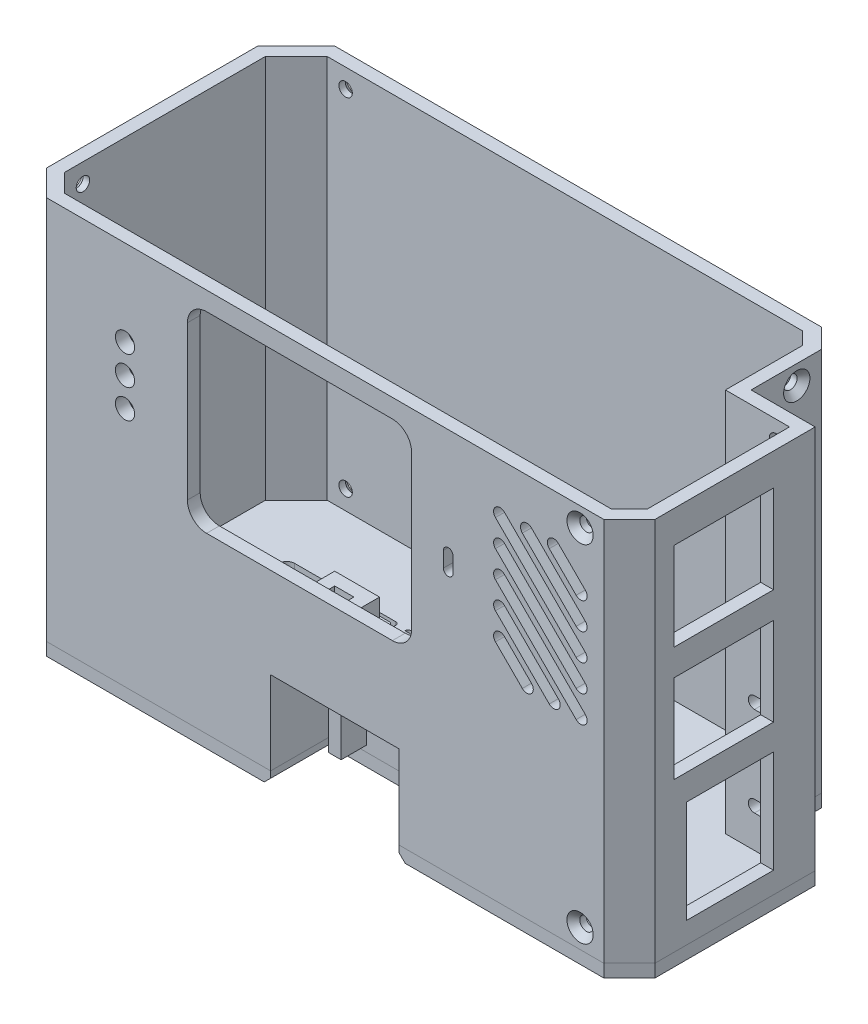
SolidWorks part; units mm, degrees
ref_plane "前视基准面" through (0, 0, 0) normal (0, 0, 1) x (1, 0, 0)
ref_plane "上视基准面" through (0, 0, 0) normal (0, 1, 0) x (1, 0, 0)
ref_plane "右视基准面" through (0, 0, 0) normal (1, 0, 0) x (0, 0, -1)
other "Configuration Table"
sketch "草图1" plane through (0, 0, 0) normal (0, 0, 1) x (1, 0, 0)
  line L1 (-105.5174, 35.9027) -> (-10.5174, 35.9027)
  line L2 (-105.5174, 35.9027) -> (-105.5174, -26.0973)
  line L3 (-105.5174, -26.0973) -> (-10.5174, -26.0973)
  line L4 (-10.5174, 35.9027) -> (-10.5174, -26.0973)
  dimension "D1" = 62
  dimension "D2" = 95
extrude "凸台-拉伸1" add sketch "草图1" along normal blind 43
sketch "草图4" plane through (0, -26.0973, 0) normal (0, -1, 0) x (1, 0, 0)
  line L0 (-10.5174, 43) -> (-10.5174, 0) construction
  line L1 (-10.5174, 14) -> (-20.5174, 14)
  line L2 (-10.5174, 14) -> (-10.5174, 0)
  line L3 (-10.5174, 0) -> (-20.5174, 0)
  line L4 (-20.5174, 14) -> (-20.5174, 0)
  line L5 (-105.5174, 0) -> (-10.5174, 0) construction
  dimension "D1" = 14
  dimension "D2" = 10
extrude "切除-拉伸3" cut sketch "草图4" against normal up to next
chamfer "倒角2" distance 6 angle 45 1 edges at (-105.5174, 4.9027, 0)
chamfer "倒角3" distance 4 angle 45 2 edges at (-105.5174, 4.9027, 43) (-10.5174, 4.9027, 43)
sketch "草图7" plane through (0, 0, 43) normal (0, 0, 1) x (1, 0, 0)
  line L0 (-101.5174, -26.0973) -> (-14.5174, -26.0973) construction
  line L1 (-46.5174, -26.0973) -> (-66.5174, -26.0973)
  line L2 (-46.5174, -26.0973) -> (-46.5174, -6.0973)
  line L3 (-46.5174, -6.0973) -> (-66.5174, -6.0973)
  line L4 (-66.5174, -26.0973) -> (-66.5174, -6.0973)
  line L6 (-10.5174, -26.0973) -> (-10.5174, 35.9027) construction
  dimension "D1" = 36
  dimension "D2" = 20
  dimension "D3" = 20
extrude "切除-拉伸5" cut sketch "草图7" against normal blind 10
shell "抽壳3" thickness 2 removed face at (-54.2952, 35.9027, 22)
sketch "草图9" plane through (0, -6.0973, 0) normal (0, -1, 0) x (1, 0, 0)
  line L0 (-44.5174, 41) -> (-68.5174, 41) construction
  line L1 (-46.5174, 41) -> (-66.5174, 41)
  line L2 (-46.5174, 41) -> (-46.5174, 33)
  line L3 (-46.5174, 33) -> (-66.5174, 33)
  line L4 (-66.5174, 41) -> (-66.5174, 33)
  line L5 (-66.5174, 33) -> (-46.5174, 33) construction
  line L8 (-66.5174, 33) -> (-66.5174, 43) construction
  line L9 (-46.5174, 33) -> (-46.5174, 43) construction
extrude "切除-拉伸6" cut sketch "草图9" against normal blind 10
sketch "草图10" plane through (0, -6.0973, 0) normal (0, -1, 0) x (1, 0, 0)
  line L4 (-66.5174, 43) -> (-66.5174, 41)
  line L5 (-66.5174, 41) -> (-46.5174, 41)
  line L6 (-46.5174, 41) -> (-46.5174, 43)
  line L7 (-46.5174, 43) -> (-66.5174, 43)
  line L8 (-66.5174, 43) -> (-66.5174, 41)
  line L9 (-66.5174, 41) -> (-46.5174, 41)
  line L10 (-46.5174, 41) -> (-46.5174, 43)
  line L11 (-46.5174, 43) -> (-66.5174, 43)
  dimension "D1" = 0
extrude "凸台-拉伸2" add sketch "草图10" along normal blind 5
sketch "草图11" plane through (0, 0, 43) normal (0, 0, 1) x (1, 0, 0)
  line L0 (-97.0174, 3.0227) -> (-76.0174, 3.0227) construction
  line L1 (-44.5121, 32.986) -> (-79.5174, 32.986)
  line L2 (-44.5121, 32.986) -> (-44.5121, 3.0227)
  line L3 (-44.5121, 3.0227) -> (-79.5174, 3.0227)
  line L4 (-79.5174, 32.986) -> (-79.5174, 3.0227)
  arc A0 (-44.0174, 32.8768) -> (-45.0174, 33.0227) centre (-45.0174, 29.5227) ccw construction
extrude "切除-拉伸7" cut sketch "草图11" against normal blind 2
fillet "圆角5" radius 3 4 edges at (-79.5174, 32.986, 42) (-79.5174, 3.0227, 42) (-44.5121, 32.986, 42) (-44.5121, 3.0227, 42)
sketch "草图12" plane through (0, 0, 33) normal (0, 0, 1) x (1, 0, 0)
  line L0 (-46.5174, -4.0973) -> (-66.5174, -4.0973) construction
  line L1 (-63.5174, -4.0973) -> (-49.5174, -4.0973)
  line L2 (-63.5174, -4.0973) -> (-63.5174, -23.0973)
  line L3 (-63.5174, -23.0973) -> (-49.5174, -23.0973)
  line L4 (-49.5174, -4.0973) -> (-49.5174, -23.0973)
  line L5 (-66.5174, -4.0973) -> (-66.5174, -11.0973) construction
  line L6 (-46.5174, -4.0973) -> (-46.5174, -11.0973) construction
  line L7 (-66.5174, -26.0973) -> (-46.5174, -26.0973) construction
  dimension "D1" = 3
  dimension "D2" = 3
  dimension "D3" = 3
extrude "凸台-拉伸3" add sketch "草图12" along normal blind 4
sketch "草图13" plane through (0, -4.0973, 0) normal (0, 1, 0) x (1, 0, 0)
  line L0 (-44.5174, -31) -> (-68.5174, -31) construction
  line L1 (-61.5174, -31) -> (-51.5174, -31)
  line L2 (-61.5174, -31) -> (-61.5174, -35.5752)
  line L3 (-61.5174, -35.5752) -> (-51.5174, -35.5752)
  line L4 (-51.5174, -31) -> (-51.5174, -35.5752)
  line L5 (-68.5174, -31) -> (-68.5174, -41) construction
  line L6 (-44.5174, -31) -> (-44.5174, -41) construction
  dimension "D1" = 7
  dimension "D2" = 7
extrude "切除-拉伸8" cut sketch "草图13" against normal blind 17
sketch "草图14" plane through (0, 0, 37) normal (0, 0, 1) x (1, 0, 0)
  line L0 (-63.5174, -23.0973) -> (-49.5174, -23.0973) construction
  line L1 (-61.5174, -4.0973) -> (-51.5174, -4.0973)
  line L2 (-61.5174, -4.0973) -> (-61.5174, -23.0973)
  line L3 (-61.5174, -23.0973) -> (-51.5174, -23.0973)
  line L4 (-51.5174, -4.0973) -> (-51.5174, -23.0973)
extrude "切除-拉伸9" cut sketch "草图14" against normal up to surface (4 mm away) up to face at (-56.5174, -14.3473, 33)
chamfer "倒角4" distance 1 angle 45 2 edges at (-66.5174, -26.0973, 38) (-46.5174, -26.0973, 38)
sketch "草图15" plane through (-10.5174, 0, 0) normal (1, 0, 0) x (0, 0, -1)
  line L1 (-34.05, -4.7773) -> (-20.5, -4.7773)
  line L2 (-34.05, -4.7773) -> (-34.05, -20.7773)
  line L3 (-34.05, -20.7773) -> (-20.5, -20.7773)
  line L4 (-20.5, -4.7773) -> (-20.5, -20.7773)
  line L5 (-36, 13.0027) -> (-20.5, 13.0027)
  line L6 (-36, 13.0027) -> (-36, -0.7573)
  line L7 (-36, -0.7573) -> (-20.5, -0.7573)
  line L8 (-20.5, 13.0027) -> (-20.5, -0.7573)
  line L9 (-36, 30.9027) -> (-20.5, 30.9027)
  line L10 (-36, 30.9027) -> (-36, 17.1427)
  line L11 (-36, 17.1427) -> (-20.5, 17.1427)
  line L12 (-20.5, 30.9027) -> (-20.5, 17.1427)
extrude "切除-拉伸10" cut sketch "草图15" against normal blind 2
sketch "草图16" plane through (0, 0, 43) normal (0, 0, 1) x (1, 0, 0)
  line L0 (-38.7974, 19.2043) -> (-38.7974, 16.8043) construction
  line L1 (-38.0444, 19.2043) -> (-38.0444, 16.8043)
  line L2 (-39.5504, 19.2043) -> (-39.5504, 16.8043)
  line L3 (-44.5121, 29.986) -> (-44.5121, 6.0227) construction
  line L5 (-44.5121, 18.0043) -> (-51.3378, 18.0043) construction
  line L6 (-10.5174, -26.0973) -> (-10.5174, 35.9027) construction
  arc A0 (-38.0444, 19.2043) -> (-39.5504, 19.2043) centre (-38.7974, 19.2043) ccw
  arc A1 (-39.5504, 16.8043) -> (-38.0444, 16.8043) centre (-38.7974, 16.8043) ccw
  point P2 (-38.7974, 18.0043)
  point P14 (-44.5121, 18.0043)
  dimension "D1" = 2.4
  dimension "D2" = 28.28
extrude "切除-拉伸11" cut sketch "草图16" against normal blind 2
sketch "草图17" plane through (0, -26.0973, 0) normal (0, -1, 0) x (1, 0, 0)
  line L0 (-105.5174, 39) -> (-105.5174, 6) construction
  line L1 (-93.9174, 13.067) -> (-84.4174, 13.067)
  line L2 (-93.9174, 13.067) -> (-93.9174, 16.567)
  line L3 (-93.9174, 16.567) -> (-84.4174, 16.567)
  line L4 (-84.4174, 13.067) -> (-84.4174, 16.567)
  line L6 (-93.9174, 20.3114) -> (-84.4174, 20.3114)
  line L7 (-93.9174, 20.3114) -> (-93.9174, 23.8114)
  line L8 (-93.9174, 23.8114) -> (-84.4174, 23.8114)
  line L9 (-84.4174, 20.3114) -> (-84.4174, 23.8114)
  line L10 (-78.1448, 23.5342) -> (-71.5448, 23.5342)
  line L11 (-78.1448, 23.5342) -> (-78.1448, 20.3114)
  line L12 (-78.1448, 20.3114) -> (-71.5448, 20.3114)
  line L13 (-71.5448, 23.5342) -> (-71.5448, 20.3114)
  line L14 (-64.6448, 23.6466) -> (-58.0448, 23.6466)
  line L15 (-64.6448, 23.6466) -> (-64.6448, 20.3114)
  line L16 (-64.6448, 20.3114) -> (-58.0448, 20.3114)
  line L17 (-58.0448, 23.6466) -> (-58.0448, 20.3114)
  line L19 (-83.4263, 17.1002) -> (-76.4263, 17.1002)
  line L20 (-83.4263, 17.1002) -> (-83.4263, 13.067)
  line L21 (-83.4263, 13.067) -> (-76.4263, 13.067)
  line L22 (-76.4263, 17.1002) -> (-76.4263, 13.067)
  line L23 (-74.9763, 17.1002) -> (-67.9763, 17.1002)
  line L24 (-74.9763, 17.1002) -> (-74.9763, 13.067)
  line L25 (-74.9763, 13.067) -> (-67.9763, 13.067)
  line L26 (-67.9763, 17.1002) -> (-67.9763, 13.067)
  line L27 (-51.5174, 16.567) -> (-43.9374, 16.567)
  line L28 (-51.5174, 16.567) -> (-51.5174, 13.767)
  line L29 (-51.5174, 13.767) -> (-43.9374, 13.767)
  line L30 (-43.9374, 16.567) -> (-43.9374, 13.767)
  line L31 (-63.5659, 16.567) -> (-52.9233, 16.567)
  line L32 (-63.5659, 16.567) -> (-63.5659, 14.767)
  line L33 (-63.5659, 14.767) -> (-52.9233, 14.767)
  line L34 (-52.9233, 16.567) -> (-52.9233, 14.767)
  dimension "D1" = 11.6
  dimension "D2" = 27.3726
  dimension "D3" = 6.9
  dimension "D4" = 6.6
  dimension "D5" = 7
  dimension "D6" = 1.45
  dimension "D7" = 9.5
  dimension "D8" = 3.5
  dimension "D9" = 2.8
  dimension "D10" = 54
  dimension "D11" = 7.58
  dimension "D12" = 1.4059
  dimension "D13" = 1.8
extrude "切除-拉伸12" cut sketch "草图17" against normal blind 2
chamfer "倒角9" distance 1 angle 45 12 edges at (-78.1448, -24.0973, 21.9228) (-74.8448, -24.0973, 23.5342) (-71.5448, -24.0973, 21.9228) (-74.8448, -24.0973, 20.3114) (-61.3448, -24.0973, 23.6466) (-64.6448, -24.0973, 21.979) (-58.0448, -24.0973, 21.979) (-61.3448, -24.0973, 20.3114) (-51.5174, -24.0973, 15.167) (-47.7274, -24.0973, 16.567) (-43.9374, -24.0973, 15.167) (-47.7274, -24.0973, 13.767)
fillet "圆角2" radius 1.2 8 edges at (-93.9174, -25.0973, 16.567) (-84.4174, -25.0973, 16.567) (-84.4174, -25.0973, 13.067) (-93.9174, -25.0973, 13.067) (-93.9174, -25.0973, 20.3114) (-93.9174, -25.0973, 23.8114) (-84.4174, -25.0973, 23.8114) (-84.4174, -25.0973, 20.3114)
fillet "圆角3" radius 0.5 18 edges at (-43.9374, -25.5973, 13.767) (-51.5174, -25.5973, 13.767) (-64.6448, -25.5973, 23.6466) (-58.0448, -25.5973, 23.6466) (-71.5448, -25.5973, 23.5342) (-78.1448, -25.5973, 23.5342) (-67.9763, -25.0973, 17.1002) (-74.9763, -25.0973, 17.1002) (-76.4263, -25.0973, 17.1002) (-83.4263, -25.0973, 17.1002) (-83.4263, -25.0973, 13.067) (-74.9763, -25.0973, 13.067) (-76.4263, -25.0973, 13.067) (-67.9763, -25.0973, 13.067) (-63.5659, -25.0973, 14.767) (-63.5659, -25.0973, 16.567) (-52.9233, -25.0973, 16.567) (-52.9233, -25.0973, 14.767)
chamfer "倒角7" distance 1 angle 45 6 edges at (-51.5174, -25.5973, 16.567) (-43.9374, -25.5973, 16.567) (-58.0448, -25.5973, 20.3114) (-64.6448, -25.5973, 20.3114) (-78.1448, -25.5973, 20.3114) (-71.5448, -25.5973, 20.3114)
sketch "草图18" plane through (0, 0, 43) normal (0, 0, 1) x (1, 0, 0)
  line L1 (-79.5174, 18.0043) -> (-81.9758, 18.0043) construction
  circle A0 centre (-89.2561, 13.5043) radius 1.5
  circle A1 centre (-89.2561, 18.0043) radius 1.5
  circle A2 centre (-89.2561, 22.5043) radius 1.5
  dimension "D3" = 3
  dimension "D2" = 3
extrude "切除-拉伸13" cut sketch "草图18" against normal blind 2
sketch "草图20" plane through (0, -24.0973, 0) normal (0, 1, 0) x (1, 0, 0)
  line L1 (-83.4263, -13.567) -> (-76.9263, -13.567)
  line L2 (-83.4263, -13.567) -> (-83.4263, -16.6002)
  line L3 (-83.4263, -16.6002) -> (-76.9263, -16.6002)
  line L4 (-76.9263, -13.567) -> (-76.9263, -16.6002)
  line L5 (-74.9763, -13.567) -> (-68.4763, -13.567)
  line L6 (-74.9763, -13.567) -> (-74.9763, -16.6002)
  line L7 (-74.9763, -16.6002) -> (-68.4763, -16.6002)
  line L8 (-68.4763, -13.567) -> (-68.4763, -16.6002)
extrude "凸台-拉伸4" add sketch "草图20" against normal blind 1
sketch "草图21" plane through (0, -25.0973, 0) normal (0, -1, 0) x (1, 0, 0)
  line L0 (-76.9263, 13.567) -> (-83.4263, 13.567) construction
  line L1 (-76.9263, 16.6002) -> (-80.9263, 16.6002)
  line L2 (-76.9263, 16.6002) -> (-76.9263, 13.567)
  line L3 (-76.9263, 13.567) -> (-80.9263, 13.567)
  line L4 (-80.9263, 16.6002) -> (-80.9263, 13.567)
  line L5 (-68.4763, 13.567) -> (-74.9763, 13.567) construction
  line L6 (-68.4763, 16.6002) -> (-72.4763, 16.6002)
  line L7 (-68.4763, 16.6002) -> (-68.4763, 13.567)
  line L8 (-68.4763, 13.567) -> (-72.4763, 13.567)
  line L9 (-72.4763, 16.6002) -> (-72.4763, 13.567)
  dimension "D1" = 4
extrude "凸台-拉伸5" add sketch "草图21" along normal up to surface (1 mm away) up to face at (-61.3448, -26.0973, 22.1299)
fillet "圆角4" radius 0.5 10 edges at (-74.9763, -25.0973, 15.0836) (-83.4263, -25.0973, 15.0836) (-80.9263, -25.5973, 13.567) (-80.9263, -25.5973, 16.6002) (-72.4763, -25.5973, 16.6002) (-72.4763, -25.5973, 13.567) (-68.4763, -25.0973, 16.6002) (-68.4763, -25.0973, 13.567) (-76.9263, -25.0973, 13.567) (-76.9263, -25.0973, 16.6002)
chamfer "倒角10" distance 2 angle 45 1 edges at (-22.5174, 5.9027, 2)
chamfer "倒角11" distance 3 angle 45 1 edges at (-20.5174, 4.9027, 0)
sketch "草图26" plane through (-20.5174, 0, 0) normal (1, 0, 0) x (0, 0, -1)
  line L0 (-10, 18.9027) -> (-10, -21.0973) construction
  line L1 (-8.6566, 18.9027) -> (-8.6566, -21.0973)
  line L2 (-11.3434, 18.9027) -> (-11.3434, -21.0973)
  line L3 (-14, -26.0973) -> (-3, -26.0973) construction
  line L5 (0, 35.9027) -> (0, -26.0973) construction
  arc A0 (-8.6566, 18.9027) -> (-11.3434, 18.9027) centre (-10, 18.9027) ccw
  arc A1 (-11.3434, -21.0973) -> (-8.6566, -21.0973) centre (-10, -21.0973) ccw
  point P2 (-10, -1.0973)
  dimension "D1" = 40
  dimension "D2" = 25
  dimension "D3" = 10
extrude "切除-拉伸15" cut sketch "草图26" against normal up to next
sketch "草图27" plane through (0, 0, 43) normal (0, 0, 1) x (1, 0, 0)
  line L0 (-10.5174, 35.9027) -> (-10.5174, -26.0973) construction
  line L2 (-22.3174, 28.4027) -> (-18.1174, 24.2027) construction
  line L3 (-21.6103, 29.1098) -> (-17.4103, 24.9098)
  line L4 (-23.0245, 27.6956) -> (-18.8245, 23.4956)
  line L5 (-26.5174, 28.4027) -> (-18.1174, 20.0027) construction
  line L6 (-25.8103, 29.1098) -> (-17.4103, 20.7098)
  line L7 (-27.2245, 27.6956) -> (-18.8245, 19.2956)
  line L8 (-30.7174, 28.4027) -> (-18.1174, 15.8027) construction
  line L9 (-30.0103, 29.1098) -> (-17.4103, 16.5098)
  line L10 (-31.4245, 27.6956) -> (-18.8245, 15.0956)
  line L11 (-30.7174, 24.2027) -> (-18.1174, 11.6027) construction
  line L12 (-30.0103, 24.9098) -> (-17.4103, 12.3098)
  line L13 (-31.4245, 23.4956) -> (-18.8245, 10.8956)
  line L14 (-30.7174, 20.0027) -> (-18.1174, 7.4027) construction
  line L15 (-30.0103, 20.7098) -> (-17.4103, 8.1098)
  line L16 (-31.4245, 19.2956) -> (-18.8245, 6.6956)
  line L17 (-22.3174, 7.4027) -> (-30.7174, 15.8027) construction
  line L18 (-23.0245, 6.6956) -> (-31.4245, 15.0956)
  line L19 (-21.6103, 8.1098) -> (-30.0103, 16.5098)
  line L20 (-30.7174, 11.6027) -> (-26.5174, 7.4027) construction
  line L21 (-30.0103, 12.3098) -> (-25.8103, 8.1098)
  line L22 (-31.4245, 10.8956) -> (-27.2245, 6.6956)
  line L23 (-14.5174, 35.9027) -> (-101.5174, 35.9027) construction
  circle A0 centre (-18.1174, 28.4027) radius 1 construction
  circle A1 centre (-22.3174, 28.4027) radius 1 construction
  circle A2 centre (-26.5174, 28.4027) radius 1 construction
  circle A3 centre (-30.7174, 28.4027) radius 1 construction
  circle A6 centre (-30.7174, 24.2027) radius 1 construction
  circle A9 centre (-30.7174, 20.0027) radius 1 construction
  circle A12 centre (-30.7174, 15.8027) radius 1 construction
  circle A15 centre (-30.7174, 11.6027) radius 1 construction
  circle A16 centre (-22.3174, 7.4027) radius 1 construction
  circle A17 centre (-26.5174, 7.4027) radius 1 construction
  circle A18 centre (-30.7174, 7.4027) radius 1 construction
  circle A25 centre (-18.1174, 24.2027) radius 1 construction
  circle A26 centre (-18.1174, 20.0027) radius 1 construction
  circle A27 centre (-18.1174, 15.8027) radius 1 construction
  circle A28 centre (-18.1174, 11.6027) radius 1 construction
  circle A29 centre (-18.1174, 7.4027) radius 1 construction
  circle A31 centre (-22.3174, 24.2027) radius 1 [skipped]
  circle A32 centre (-26.5174, 24.2027) radius 1 [skipped]
  circle A33 centre (-22.3174, 20.0027) radius 1 [skipped]
  circle A34 centre (-26.5174, 20.0027) radius 1 [skipped]
  circle A35 centre (-22.3174, 15.8027) radius 1 [skipped]
  circle A36 centre (-26.5174, 15.8027) radius 1 [skipped]
  circle A37 centre (-22.3174, 11.6027) radius 1 [skipped]
  circle A38 centre (-26.5174, 11.6027) radius 1 [skipped]
  arc A39 (-21.6103, 29.1098) -> (-23.0245, 27.6956) centre (-22.3174, 28.4027) ccw
  arc A40 (-18.8245, 23.4956) -> (-17.4103, 24.9098) centre (-18.1174, 24.2027) ccw
  arc A41 (-25.8103, 29.1098) -> (-27.2245, 27.6956) centre (-26.5174, 28.4027) ccw
  arc A42 (-18.8245, 19.2956) -> (-17.4103, 20.7098) centre (-18.1174, 20.0027) ccw
  arc A43 (-30.0103, 29.1098) -> (-31.4245, 27.6956) centre (-30.7174, 28.4027) ccw
  arc A44 (-18.8245, 15.0956) -> (-17.4103, 16.5098) centre (-18.1174, 15.8027) ccw
  arc A45 (-30.0103, 24.9098) -> (-31.4245, 23.4956) centre (-30.7174, 24.2027) ccw
  arc A46 (-18.8245, 10.8956) -> (-17.4103, 12.3098) centre (-18.1174, 11.6027) ccw
  arc A47 (-30.0103, 20.7098) -> (-31.4245, 19.2956) centre (-30.7174, 20.0027) ccw
  arc A48 (-18.8245, 6.6956) -> (-17.4103, 8.1098) centre (-18.1174, 7.4027) ccw
  arc A49 (-23.0245, 6.6956) -> (-21.6103, 8.1098) centre (-22.3174, 7.4027) ccw
  arc A50 (-30.0103, 16.5098) -> (-31.4245, 15.0956) centre (-30.7174, 15.8027) ccw
  arc A51 (-30.0103, 12.3098) -> (-31.4245, 10.8956) centre (-30.7174, 11.6027) ccw
  arc A52 (-27.2245, 6.6956) -> (-25.8103, 8.1098) centre (-26.5174, 7.4027) ccw
  point P4 (-20.2174, 26.3027)
  point P17 (-22.3174, 24.2027)
  point P24 (-24.4174, 22.1027)
  point P33 (-24.4174, 17.9027)
  point P46 (-24.4174, 13.7027)
  point P51 (-26.5174, 11.6027)
  point P56 (-28.6174, 9.5027)
  dimension "D3" = 2
  dimension "D1" = 7.6
  dimension "D2" = 7.5
  dimension "D4" = 4
  dimension "D5" = 6
sketch "草图29" plane through (-105.5174, 0, 0) normal (-1, 0, 0) x (0, 0, 1)
  line L0 (39, -26.0973) -> (6, -26.0973) construction
  circle A0 centre (35.3017, 32.9027) radius 1.05
  circle A1 centre (35.3017, -21.0973) radius 1.2021
  dimension "D1" = 2.1
  dimension "D2" = 5
extrude "切除-拉伸18" cut sketch "草图29" against normal up to next
sketch "草图30" plane through (0, 0, 0) normal (0, 0, -1) x (-1, 0, 0)
  line L0 (99.5174, -26.0973) -> (23.5174, -26.0973) construction
  circle A0 centre (95.8191, 32.9027) radius 1.05
  circle A1 centre (95.8191, -21.0973) radius 1.05
  dimension "D1" = 2.1
  dimension "D2" = 5
extrude "切除-拉伸19" cut sketch "草图30" against normal up to next
sketch "草图31" plane through (-20.5174, 0, 0) normal (1, 0, 0) x (0, 0, -1)
  line L0 (-14, -26.0973) -> (-3, -26.0973) construction
  circle A0 centre (-6.8698, 32.9027) radius 1.05
  circle A1 centre (-6.8698, -21.0973) radius 1.05
  dimension "D1" = 2.1
  dimension "D2" = 5
extrude "切除-拉伸20" cut sketch "草图31" against normal up to next
sketch "草图32" plane through (0, 0, 14) normal (0, 0, -1) x (-1, 0, 0)
  line L0 (10.5174, -26.0973) -> (20.5174, -26.0973) construction
  circle A0 centre (14.6174, 32.9027) radius 1.05
  circle A1 centre (14.6174, -21.0973) radius 1.05
  dimension "D1" = 2.1
  dimension "D2" = 5
extrude "切除-拉伸21" cut sketch "草图32" against normal up to next
sketch "草图33" plane through (0, 0, 43) normal (0, 0, 1) x (1, 0, 0)
  line L1 (-45.5174, -26.0973) -> (-14.5174, -26.0973) construction
  circle A0 centre (-18.2157, 32.9027) radius 1.05
  circle A1 centre (-18.2157, -21.0973) radius 1.05
  dimension "D1" = 2.1
  dimension "D2" = 5
extrude "切除-拉伸22" cut sketch "草图33" against normal up to next
chamfer "倒角20" distance 1 angle 45 10 edges at (-96.8691, 32.9027, 0) (-105.5174, 31.8527, 35.3017) (-17.1657, 32.9027, 43) (-15.6674, 32.9027, 14) (-20.5174, 32.9027, 5.8198) (-17.1657, -21.0973, 43) (-15.6674, -21.0973, 14) (-96.8691, -21.0973, 0) (-105.5174, -22.2995, 35.3017) (-20.5174, -21.0973, 5.8198)
sketch "草图34" plane through (0, 0, 14) normal (0, 0, -1) x (-1, 0, 0)
  line L0 (18.0174, -4.0973) -> (14.0174, -4.0973) construction
  line L1 (18.0174, -5.0973) -> (14.0174, -5.0973)
  line L2 (18.0174, -3.0973) -> (14.0174, -3.0973)
  line L3 (18.0174, -18.0973) -> (14.0174, -18.0973) construction
  line L4 (18.0174, -19.0973) -> (14.0174, -19.0973)
  line L5 (18.0174, -17.0973) -> (14.0174, -17.0973)
  line L7 (20.5174, 35.9027) -> (20.5174, -26.0973) construction
  arc A0 (18.0174, -5.0973) -> (18.0174, -3.0973) centre (18.0174, -4.0973) ccw
  arc A1 (14.0174, -3.0973) -> (14.0174, -5.0973) centre (14.0174, -4.0973) ccw
  arc A2 (18.0174, -19.0973) -> (18.0174, -17.0973) centre (18.0174, -18.0973) ccw
  arc A3 (14.0174, -17.0973) -> (14.0174, -19.0973) centre (14.0174, -18.0973) ccw
  point P3 (16.0174, -4.0973)
  point P8 (16.0174, -18.0973)
  dimension "D1" = 1
  dimension "D2" = 4
  dimension "D3" = 2.5
  dimension "D4" = 14
extrude "切除-拉伸25" cut sketch "草图34" against normal up to next (2 mm away) draft 2
extrude "切除-拉伸26" cut sketch "草图27" against normal up to next
split "分割1" bodies to split 138 resulting bodies 139 140 split by face at (-47.7274, -24.0973, 15.167)
